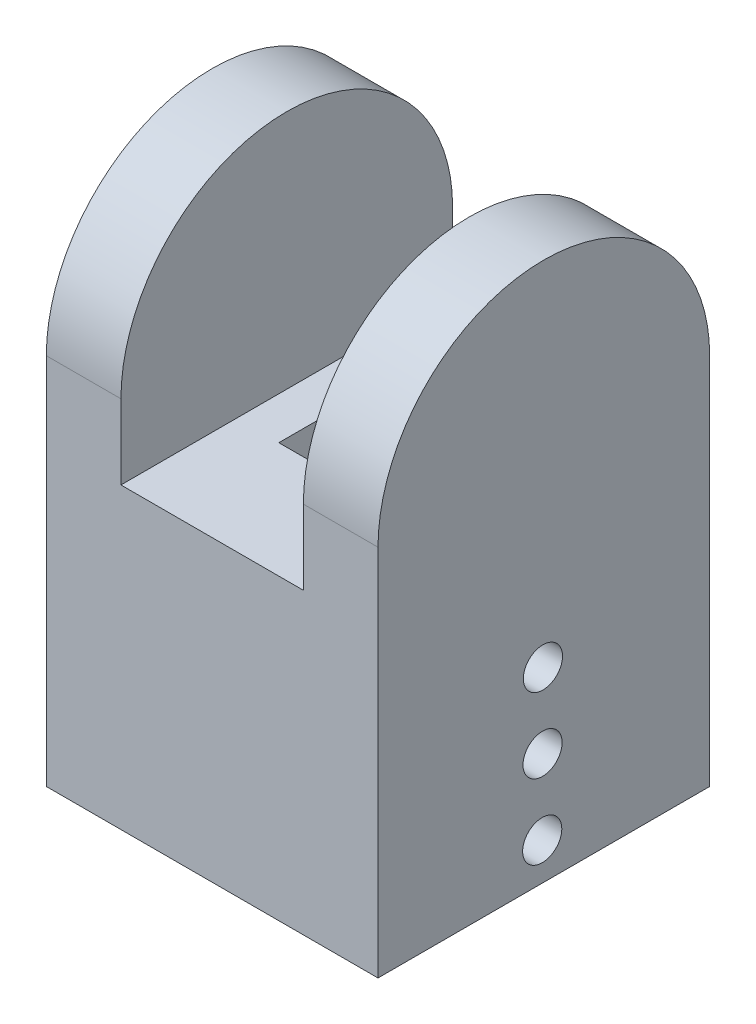
SolidWorks part; units mm, degrees
ref_plane "Front Plane" through (0, 0, 0) normal (0, 0, 1) x (1, 0, 0)
ref_plane "Top Plane" through (0, 0, 0) normal (0, 1, 0) x (1, 0, 0)
ref_plane "Right Plane" through (0, 0, 0) normal (1, 0, 0) x (0, 0, -1)
sketch "Sketch1" plane through (0, 0, 0) normal (0, 1, 0) x (1, 0, 0)
  line L0 (-46.6727, -43.9684) -> (42.2273, -43.9684)
  line L1 (-46.6727, -43.9684) -> (-46.6727, 44.9316)
  line L2 (-46.6727, 44.9316) -> (42.2273, 44.9316)
  line L3 (42.2273, -43.9684) -> (42.2273, 44.9316)
  line L8 (0, 0) -> (10.8773, 0)
  line L9 (10.8773, 0) -> (10.8773, 13.2)
  line L10 (10.8773, 13.2) -> (-15.3227, 13.2)
  line L11 (-15.3227, 13.2) -> (-15.3227, -13)
  line L12 (-15.3227, -13) -> (10.8773, -13)
  line L13 (10.8773, -13) -> (10.8773, 0)
  dimension "D1" = 88.9
  dimension "D2" = 88.9
  dimension "D3" = 26.2
  dimension "D4" = 26.2
  dimension "D5" = 13
  dimension "D6" = 31.35
extrude "Boss-Extrude1" add sketch "Sketch1" along normal blind 100 contours L0 L3 L2 L1 region at (-45.4155, 0, -0.4816)
sketch "Sketch2" plane through (42.2273, 0, 0) normal (1, 0, 0) x (0, 0, -1)
  line L0 (0.4816, 100) -> (0, 0)
  line L1 (-43.9684, 100) -> (44.9316, 100) construction
  line L2 (-43.9684, 0) -> (44.9316, 0) construction
  circle A2 centre (0.0482, 10) radius 5.25
  circle A3 centre (0.1445, 30) radius 5.25
  circle A4 centre (0.2408, 49.9998) radius 5.25
  point P15 (-47.747, 83.7198)
  dimension "D1" = 10
  dimension "D2" = 20
  dimension "D3" = 20
extrude "Cut-Extrude1" cut sketch "Sketch2" against normal blind 101 contours L0 A4 | L0 A4 | L0 A3 | L0 A3 | L0 A2 | L0 A2 region at (42.2273, 49.989, -2.4689) region at (42.2273, 9.9893, -2.2763) region at (42.2273, 10.0107, 2.18) region at (42.2273, 29.9893, -2.3726) region at (42.2273, 30.0107, 2.0837) region at (42.2273, 50.0105, 1.9874)
fillet "Fillet1" [suppressed] radius 20
sketch "Sketch3" plane through (42.2273, 0, 0) normal (1, 0, 0) x (0, 0, -1)
  line L0 (-43.9684, 100) -> (44.9316, 100) construction
  line L1 (-43.9684, 100) -> (44.9316, 100)
  arc A0 (44.9316, 100) -> (-43.9684, 100) centre (0.4816, 100) ccw
sketch "Sketch4" plane through (-46.6727, 0, 0) normal (-1, 0, 0) x (0, 0, 1)
  line L0 (43.9684, 100) -> (-44.9316, 100) construction
  line L1 (-44.9316, 100) -> (43.9684, 100)
  arc A0 (43.9684, 100) -> (-44.9316, 100) centre (-0.4816, 100) ccw
extrude "Boss-Extrude2" add sketch "Sketch3" against normal blind 20
extrude "Boss-Extrude3" add sketch "Sketch4" against normal blind 20
sketch "Sketch5" plane through (0, 0, 43.9684) normal (0, 0, 1) x (1, 0, 0)
  line L1 (-26.6727, 100) -> (22.2273, 100)
  line L2 (-26.6727, 100) -> (-26.6727, 80)
  line L3 (-26.6727, 80) -> (22.2273, 80)
  line L4 (22.2273, 100) -> (22.2273, 80)
  dimension "D1" = 20
extrude "Cut-Extrude2" cut sketch "Sketch5" against normal blind 120
